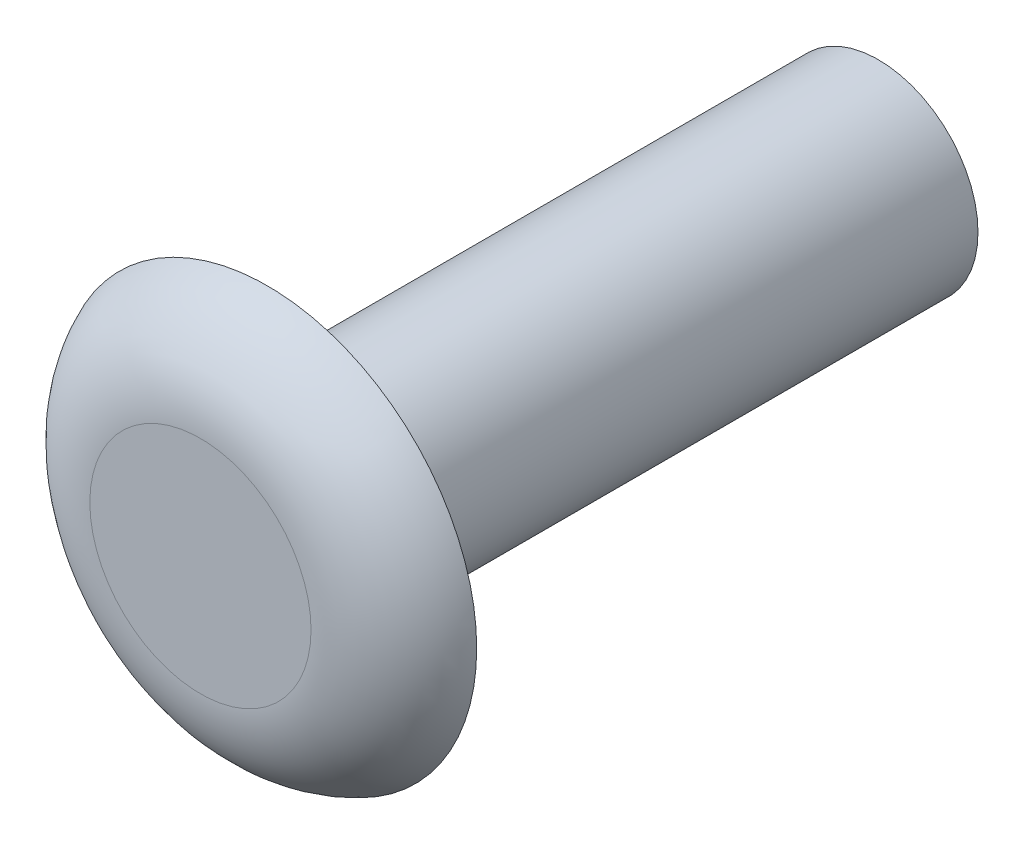
SolidWorks part; units mm, degrees
ref_plane "Front Plane" through (0, 0, 0) normal (0, 0, 1) x (1, 0, 0)
ref_plane "Top Plane" through (0, 0, 0) normal (0, 1, 0) x (1, 0, 0)
ref_plane "Right Plane" through (0, 0, 0) normal (1, 0, 0) x (0, 0, -1)
sketch "Sketch1" plane through (0, 0, 0) normal (0, 0, 1) x (1, 0, 0)
  circle A0 centre (0, 0) radius 5.0038
  dimension "D1" = 10.0076
extrude "Boss-Extrude1" add sketch "Sketch1" along normal blind 1.6002
sketch "Sketch2" plane through (0, 0, 0) normal (0, 0, 1) x (1, 0, 0)
  circle A0 centre (0, 0) radius 2.3813
  dimension "D1" = 4.7625
extrude "Boss-Extrude2" add sketch "Sketch2" against normal blind 14.605
fillet "Fillet1" radius 2.54 1 edges at (5.0038, 0, 1.6002)
